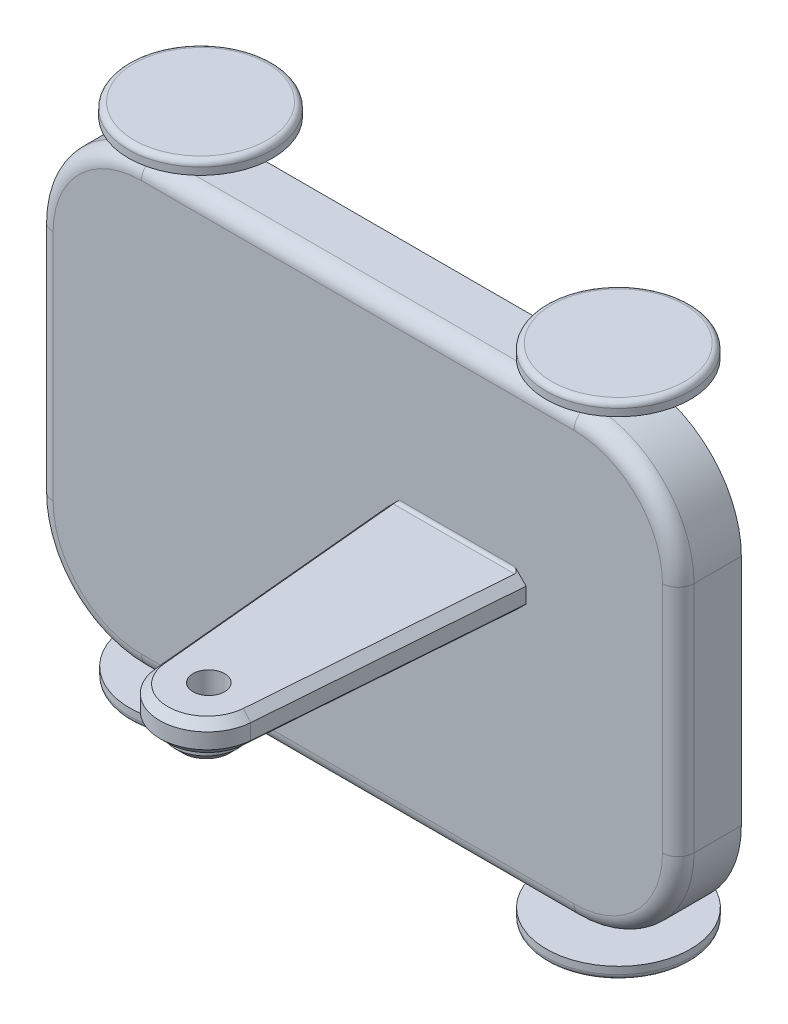
SolidWorks part; units mm, degrees
ref_plane "Front Plane" through (0, 0, 0) normal (0, 0, 1) x (1, 0, 0)
ref_plane "Top Plane" through (0, 0, 0) normal (0, 1, 0) x (1, 0, 0)
ref_plane "Right Plane" through (0, 0, 0) normal (1, 0, 0) x (0, 0, -1)
sketch "Sketch1" plane through (0, 0, 0) normal (0, 0, 1) x (1, 0, 0)
  line L1 (-100.8135, 57.8054) -> (36.3465, 57.8054)
  line L2 (-133.8335, 24.7854) -> (-133.8335, -49.1746)
  line L3 (-100.8135, -82.1946) -> (36.3465, -82.1946)
  line L4 (69.3665, 24.7854) -> (69.3665, -49.1746)
  line L5 (-133.8335, 57.8054) -> (69.3665, -82.1946) construction
  line L6 (-133.8335, -82.1946) -> (69.3665, 57.8054) construction
  arc A0 (-133.8335, -49.1746) -> (-100.8135, -82.1946) centre (-100.8135, -49.1746) ccw
  arc A1 (-100.8135, 57.8054) -> (-133.8335, 24.7854) centre (-100.8135, 24.7854) ccw
  arc A2 (36.3465, -82.1946) -> (69.3665, -49.1746) centre (36.3465, -49.1746) ccw
  arc A3 (36.3465, 57.8054) -> (69.3665, 24.7854) centre (36.3465, 24.7854) cw
  point P0 (-32.2335, -12.1946)
  dimension "D3" = 33.02
  dimension "D1" = 203.2
  dimension "D2" = 140
extrude "Boss-Extrude1" add sketch "Sketch1" along normal blind 20
fillet "Fillet1" radius 5 8 edges at (-124.1622, 48.1341, 20) (-133.8335, -12.1946, 20) (-124.1622, -72.5232, 20) (-32.2335, -82.1946, 20) (59.6952, -72.5232, 20) (59.6952, 48.1341, 20) (-32.2335, 57.8054, 20) (69.3665, -12.1946, 20)
sketch "Sketch12" plane through (0, 0, 0) normal (0, 1, 0) x (1, 0, 0)
  line L0 (21.3971, -16.5549) -> (14.9567, -101.1388)
  line L1 (-22.922, -16.5549) -> (-14.934, -101.4059)
  line L2 (-22.922, -16.5549) -> (21.3971, -16.5549)
  arc A0 (-14.934, -101.4059) -> (14.9567, -101.1388) centre (0, -100) ccw
  dimension "D1" = 100
  dimension "30mm" = 30
extrude "Boss-Extrude10" add sketch "Sketch12" along normal mid plane 10 contours L1 A0 L0 L2
chamfer "Chamfer1" distance 2.54 angle 45 3 edges at (-18.7658, -5, 60.703) (18.0457, -5, 60.5694) (0.134, -5, 114.9994)
chamfer "Chamfer2" distance 2.54 angle 45 3 edges at (-18.7658, 5, 60.703) (0.134, 5, 114.9994) (18.0457, 5, 60.5694)
sketch "Sketch13" plane through (0, -5, 0) normal (0, -1, 0) x (1, 0, 0)
  circle A0 centre (0.0751, 100.3683) radius 10
extrude "Boss-Extrude11" add sketch "Sketch13" along normal blind 5 contours A0
sketch "Sketch14" plane through (0, 5, 0) normal (0, 1, 0) x (1, 0, 0)
  circle A0 centre (-0.1262, -99.3548) radius 5
extrude "Cut-Extrude1" cut sketch "Sketch14" against normal blind 10 contours A0
chamfer "Chamfer3" distance 2.54 angle 45 1 edges at (0.0751, -10, 90.3683)
fillet "Fillet5" radius 1.016 2 edges at (-0.7295, -5, 20) (-0.7295, 5, 20)
sketch "Sketch15" plane through (0, -10, 0) normal (0, -1, 0) x (1, 0, 0)
  line L1 (3.3806, 94.8115) -> (6.549, 100.2994)
  line L2 (6.549, 100.2994) -> (3.3806, 105.7872)
  line L3 (3.3806, 105.7872) -> (-2.9562, 105.7872)
  line L4 (-2.9562, 105.7872) -> (-6.1246, 100.2994)
  line L5 (-6.1246, 100.2994) -> (-2.9562, 94.8115)
  line L6 (-2.9562, 94.8115) -> (3.3806, 94.8115)
  circle A0 centre (0.2122, 100.2994) radius 5.4878 construction
extrude "Boss-Extrude13" add sketch "Sketch15" along normal blind 0.508 contours L3 L4 L5 L6 L1 L2
fillet "Fillet6" radius 1.27 6 edges at (4.9648, -10.508, 97.5554) (0.2122, -10.508, 94.8115) (-4.5404, -10.508, 97.5554) (-4.5404, -10.508, 103.0433) (0.2122, -10.508, 105.7872) (4.9648, -10.508, 103.0433)
sketch "Sketch16" plane through (0, -82.1946, 0) normal (0, -1, 0) x (1, 0, 0)
  line L1 (-100.7563, 5.6047) -> (-96.1843, 5.6047)
  line L2 (-100.7563, 5.6047) -> (-100.7563, 1.0327)
  line L3 (-100.7563, 1.0327) -> (-96.1843, 1.0327)
  line L4 (-96.1843, 5.6047) -> (-96.1843, 1.0327)
  line L5 (-100.7563, 5.6047) -> (-96.1843, 1.0327) construction
  line L6 (-100.7563, 1.0327) -> (-96.1843, 5.6047) construction
  point P0 (-98.4703, 3.3187)
  dimension "D1" = 4.572
  dimension "D2" = 4.572
extrude "Boss-Extrude14" add sketch "Sketch16" along normal blind 5.588
sketch "Sketch17" plane through (0, -82.1946, 0) normal (0, -1, 0) x (1, 0, 0)
  line L0 (-100.7563, 1.0327) -> (-96.1843, 1.0327) construction
  line L1 (31.5396, 5.6047) -> (36.1116, 5.6047)
  line L2 (31.5396, 5.6047) -> (31.5396, 1.0327)
  line L3 (31.5396, 1.0327) -> (36.1116, 1.0327)
  line L4 (36.1116, 5.6047) -> (36.1116, 1.0327)
  line L5 (31.5396, 5.6047) -> (36.1116, 1.0327) construction
  line L6 (31.5396, 1.0327) -> (36.1116, 5.6047) construction
  point P0 (33.8256, 3.3187)
  dimension "D1" = 4.572
  dimension "D2" = 4.572
extrude "Boss-Extrude15" add sketch "Sketch17" along normal blind 5.588
sketch "Sketch18" plane through (0, 57.8054, 0) normal (0, 1, 0) x (1, 0, 0)
  line L1 (-100.7188, -1.3277) -> (-96.1468, -1.3277)
  line L2 (-100.7188, -1.3277) -> (-100.7188, -5.8997)
  line L3 (-100.7188, -5.8997) -> (-96.1468, -5.8997)
  line L4 (-96.1468, -1.3277) -> (-96.1468, -5.8997)
  line L5 (-100.7188, -1.3277) -> (-96.1468, -5.8997) construction
  line L6 (-100.7188, -5.8997) -> (-96.1468, -1.3277) construction
  point P0 (-98.4328, -3.6137)
  dimension "D1" = 4.572
  dimension "D2" = 4.572
extrude "Boss-Extrude16" add sketch "Sketch18" along normal blind 5.588
sketch "Sketch19" plane through (0, 57.8054, 0) normal (0, 1, 0) x (1, 0, 0)
  line L1 (31.6149, -1.3277) -> (36.1869, -1.3277)
  line L2 (31.6149, -1.3277) -> (31.6149, -5.8997)
  line L3 (31.6149, -5.8997) -> (36.1869, -5.8997)
  line L4 (36.1869, -1.3277) -> (36.1869, -5.8997)
  line L5 (31.6149, -1.3277) -> (36.1869, -5.8997) construction
  line L6 (31.6149, -5.8997) -> (36.1869, -1.3277) construction
  line L7 (-96.1468, -1.3277) -> (-100.7188, -1.3277) construction
  point P0 (33.9009, -3.6137)
  dimension "D1" = 4.572
  dimension "D2" = 4.572
extrude "Boss-Extrude17" add sketch "Sketch19" along normal blind 5.588 contours L1 L4 L3 L2
sketch "Sketch20" plane through (0, -87.7826, 0) normal (0, -1, 0) x (1, 0, 0)
  circle A0 centre (-98.5658, 3.1981) radius 22.86
extrude "Boss-Extrude18" add sketch "Sketch20" along normal blind 4.064
sketch "Sketch21" plane through (0, -87.7826, 0) normal (0, -1, 0) x (1, 0, 0)
  circle A0 centre (33.759, 3.3542) radius 22.86
extrude "Boss-Extrude19" add sketch "Sketch21" along normal blind 4.064
sketch "Sketch22" plane through (0, 63.3934, 0) normal (0, 1, 0) x (1, 0, 0)
  circle A0 centre (33.9993, -3.675) radius 22.86
extrude "Boss-Extrude20" add sketch "Sketch22" along normal blind 4.064 contours A0
sketch "Sketch23" plane through (0, 63.3934, 0) normal (0, 1, 0) x (1, 0, 0)
  circle A0 centre (-98.4905, -3.605) radius 22.86
extrude "Boss-Extrude21" add sketch "Sketch23" along normal blind 4.064 contours A0
fillet "Fillet7" radius 1.778 4 edges at (33.9993, 67.4574, 26.535) (-98.4905, 67.4574, 26.465) (-98.5658, -91.8466, -19.6619) (33.759, -91.8466, -19.5058)
